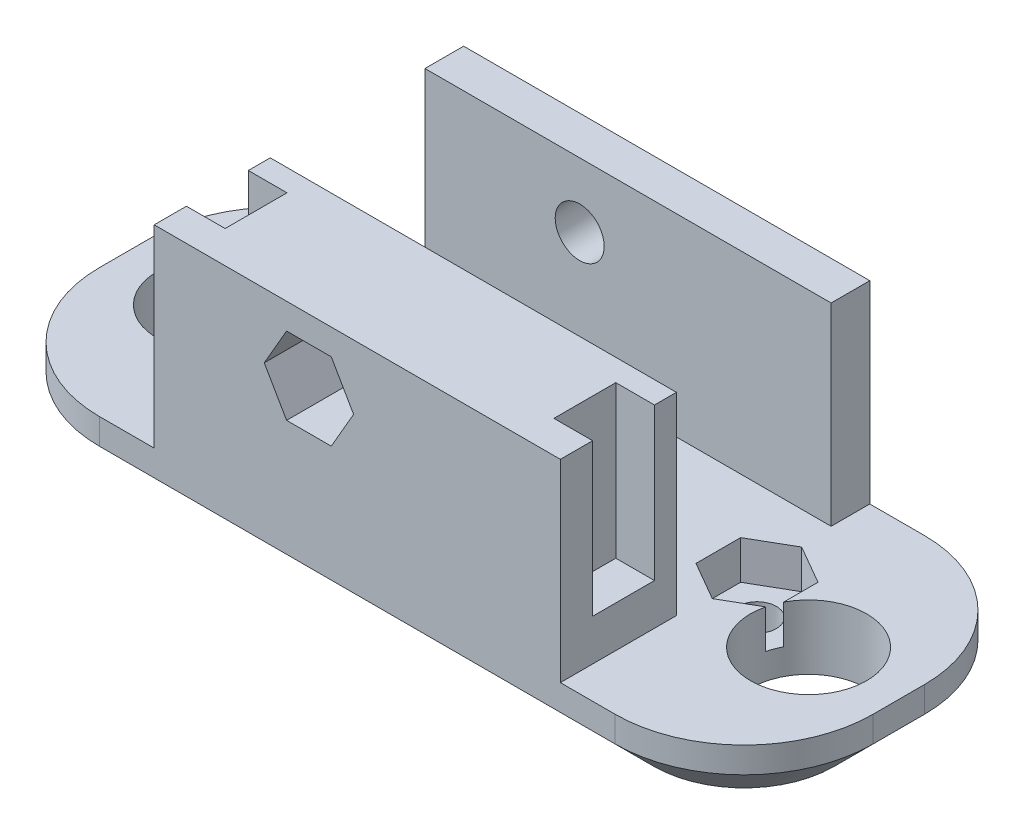
SolidWorks part; units mm, degrees
ref_plane "Спереди" through (0, 0, 0) normal (0, 0, 1) x (1, 0, 0)
ref_plane "Сверху" through (0, 0, 0) normal (0, 1, 0) x (1, 0, 0)
ref_plane "Справа" through (0, 0, 0) normal (1, 0, 0) x (0, 0, -1)
sketch "Эскиз1" plane through (0, 0, 0) normal (0, 1, 0) x (1, 0, 0)
  line L1 (0, 0) -> (60, 0)
  line L2 (0, 0) -> (0, 24)
  line L3 (0, 24) -> (60, 24)
  line L4 (60, 0) -> (60, 24)
  dimension "D1" = 60
  dimension "D2" = 24
extrude "Бобышка-Вытянуть1" add sketch "Эскиз1" along normal blind 5
sketch "Эскиз2" plane through (0, 5, 0) normal (0, 1, 0) x (1, 0, 0)
  line L0 (60, 24) -> (0, 24) construction
  line L1 (14.25, 0) -> (45.75, 0)
  line L2 (14.25, 0) -> (14.25, 9)
  line L3 (14.25, 9) -> (45.75, 9)
  line L4 (45.75, 0) -> (45.75, 9)
  line L5 (45.75, 21) -> (14.25, 21)
  line L6 (45.75, 21) -> (45.75, 24)
  line L7 (45.75, 24) -> (14.25, 24)
  line L8 (14.25, 21) -> (14.25, 24)
  line L9 (0, 0) -> (60, 0) construction
  point P12 (30, 24)
  point P13 (30, 24)
  dimension "D1" = 31.5
  dimension "D2" = 9
  dimension "D3" = 3
extrude "Бобышка-Вытянуть2" add sketch "Эскиз2" along normal blind 15
sketch "Эскиз3" plane through (0, 0, 0) normal (0, 0, 1) x (1, 0, 0)
  line L0 (14.25, 20) -> (45.75, 20) construction
  line L2 (14.25, 20) -> (14.25, 5) construction
  circle A0 centre (26.25, 15) radius 1.9
  dimension "D1" = 3.8
  dimension "D2" = 12
  dimension "D3" = 5
extrude "Вырез-Вытянуть1" cut sketch "Эскиз3" against normal blind 24
sketch "Эскиз4" plane through (0, 0, 0) normal (0, -1, 0) x (1, 0, 0)
  line L2 (7, -12) -> (53, -12) construction
  line L3 (60, -24) -> (0, -24) construction
  line L4 (45.75, 0) -> (60, 0) construction
  circle A0 centre (7, -12) radius 4.5
  circle A1 centre (53, -12) radius 4.5
  point P4 (30, -12)
  point P10 (30, -24)
  dimension "D3" = 9
  dimension "D1" = 46
  dimension "D2" = 12
extrude "Вырез-Вытянуть2" cut sketch "Эскиз4" against normal blind 24
sketch "Эскиз5" plane through (0, 5, 0) normal (0, 1, 0) x (1, 0, 0)
  line L1 (46, 15) -> (14, 15) construction
  line L2 (30, 9) -> (30, 21) construction
  line L3 (45.75, 9) -> (14.25, 9) construction
  line L4 (14.25, 21) -> (45.75, 21) construction
  line L11 (43, 16.7321) -> (43, 13.2679)
  line L12 (43, 13.2679) -> (46, 11.5359)
  line L13 (46, 11.5359) -> (49, 13.2679)
  line L14 (49, 13.2679) -> (49, 16.7321)
  line L15 (49, 16.7321) -> (46, 18.4641)
  line L16 (46, 18.4641) -> (43, 16.7321)
  line L17 (11, 16.7321) -> (11, 13.2679)
  line L18 (11, 13.2679) -> (14, 11.5359)
  line L19 (14, 11.5359) -> (17, 13.2679)
  line L20 (17, 13.2679) -> (17, 16.7321)
  line L21 (17, 16.7321) -> (14, 18.4641)
  line L22 (14, 18.4641) -> (11, 16.7321)
  circle A0 centre (46, 15) radius 3 construction
  circle A1 centre (14, 15) radius 3 construction
  point P8 (30, 15)
  point P9 (30, 15)
  dimension "D1" = 6
  dimension "D2" = 32
fillet "Скругление1" radius 10 4 edges at (60, 2.5, -24) (60, 2.5, 0) (0, 2.5, 0) (0, 2.5, -24)
extrude "Вырез-Вытянуть3" cut sketch "Эскиз5" against normal blind 3
sketch "Эскиз7" plane through (0, 2, 0) normal (0, 1, 0) x (1, 0, 0)
  line L2 (43, 16.7321) -> (43, 13.2679) construction
  circle A0 centre (14, 15) radius 1.5
  circle A1 centre (46, 15) radius 1.5
  point P9 (43, 15)
  dimension "D1" = 3
extrude "Вырез-Вытянуть4" cut sketch "Эскиз7" against normal blind 3
sketch "Эскиз8" plane through (0, 0, 0) normal (0, 0, 1) x (1, 0, 0)
  line L0 (14.25, 20) -> (45.75, 20) construction
  line L1 (27.9821, 18) -> (24.5179, 18)
  line L2 (24.5179, 18) -> (22.7859, 15)
  line L3 (22.7859, 15) -> (24.5179, 12)
  line L4 (24.5179, 12) -> (27.9821, 12)
  line L5 (27.9821, 12) -> (29.7141, 15)
  line L6 (29.7141, 15) -> (27.9821, 18)
  circle A0 centre (26.25, 15) radius 3 construction
  dimension "D1" = 6
extrude "Вырез-Вытянуть5" cut sketch "Эскиз8" against normal blind 6
sketch "Эскиз9" plane through (14.25, 0, 0) normal (-1, 0, 0) x (0, 0, 1)
  line L0 (-9, 20) -> (-9, 5) construction
  line L1 (-2.5, 8.2063) -> (-7.3, 8.2063)
  line L2 (-2.5, 8.2063) -> (-2.5, 20.6838)
  line L3 (-2.5, 20.6838) -> (-7.3, 20.6838)
  line L4 (-7.3, 8.2063) -> (-7.3, 20.6838)
  line L5 (0, 20) -> (0, 5) construction
  dimension "D1" = 1.7
  dimension "D2" = 2.5
extrude "Вырез-Вытянуть6" cut sketch "Эскиз9" against normal blind 3
sketch "Эскиз10" plane through (45.75, 0, 0) normal (1, 0, 0) x (0, 0, -1)
  line L1 (2.5, 8.2063) -> (7.3, 8.2063)
  line L2 (2.5, 8.2063) -> (2.5, 37.3786)
  line L3 (2.5, 37.3786) -> (7.3, 37.3786)
  line L4 (7.3, 8.2063) -> (7.3, 37.3786)
extrude "Вырез-Вытянуть7" cut sketch "Эскиз10" against normal blind 3
chamfer "Фаска1" distance 3 angle 45 8 edges at (30, 0, -24) (2.9289, 0, -21.0711) (57.0711, 0, -21.0711) (0, 0, -12) (60, 0, -12) (2.9289, 0, -2.9289) (57.0711, 0, -2.9289) (30, 0, 0)
